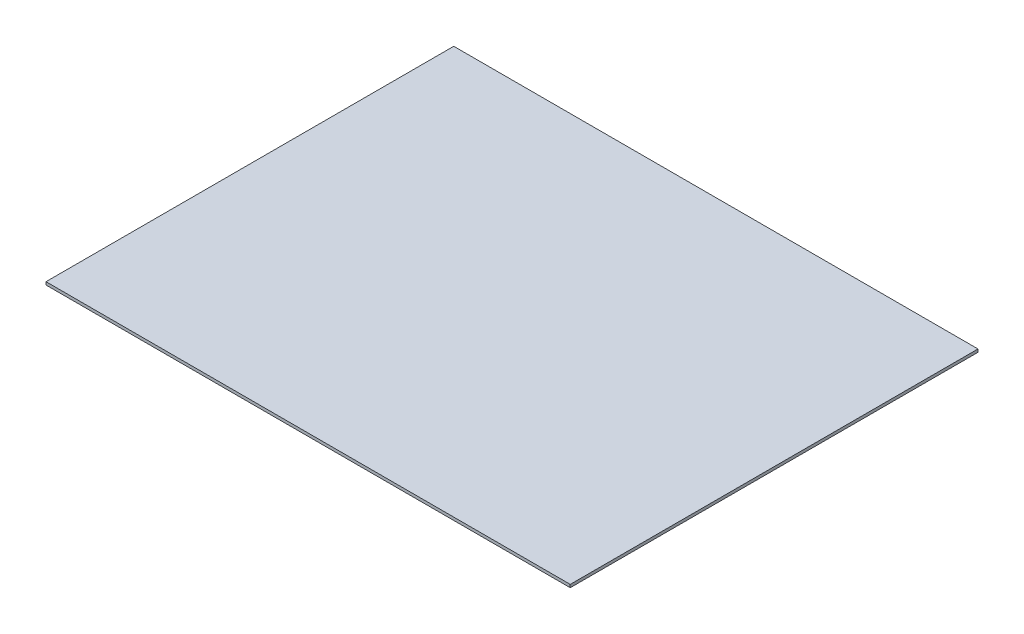
SolidWorks part; units mm, degrees
ref_plane "Front Plane" through (0, 0, 0) normal (0, 0, 1) x (1, 0, 0)
ref_plane "Top Plane" through (0, 0, 0) normal (0, 1, 0) x (1, 0, 0)
ref_plane "Right Plane" through (0, 0, 0) normal (1, 0, 0) x (0, 0, -1)
sketch "Sketch1" plane through (0, 0, 0) normal (0, 1, 0) x (1, 0, 0)
  line L1 (-90, -70) -> (90, -70)
  line L2 (-90, -70) -> (-90, 70)
  line L3 (-90, 70) -> (90, 70)
  line L4 (90, -70) -> (90, 70)
  line L5 (-90, -70) -> (90, 70) construction
  line L6 (-90, 70) -> (90, -70) construction
  point P0 (0, 0)
  dimension "D1" = 180
  dimension "D2" = 140
extrude "Boss-Extrude1" add sketch "Sketch1" along normal blind 1
